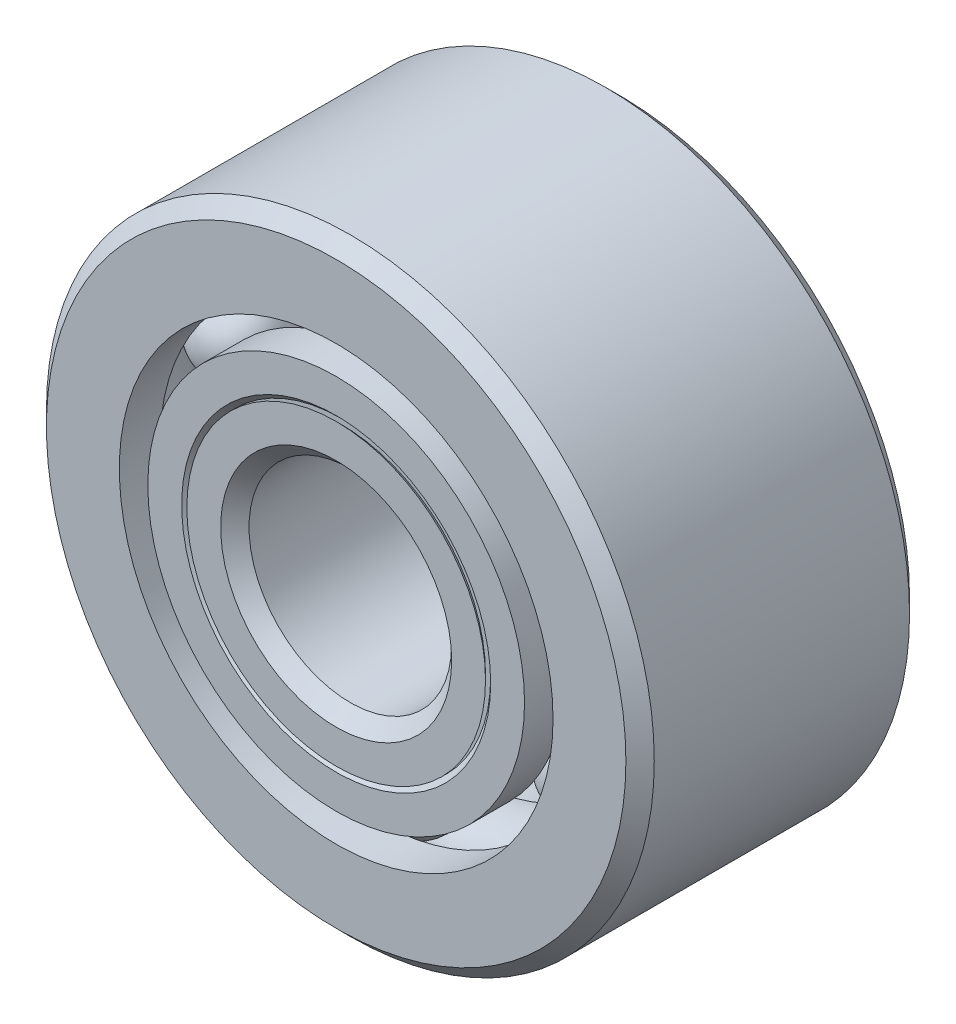
SolidWorks part; units mm, degrees
note: '?' marks a value the reader was unsure of.
ref_plane "Front Plane" through (0, 0, 0) normal (0, 0, 1) x (1, 0, 0)
ref_plane "Top Plane" through (0, 0, 0) normal (0, 1, 0) x (1, 0, 0)
ref_plane "Right Plane" through (0, 0, 0) normal (1, 0, 0) x (0, 0, -1)
sketch "Sketch1" plane through (0, 0, 0) normal (1, 0, 0) x (0, 0, -1)
  line L0 (-7, 0) -> (7, 0) construction
  line L1 (0, 15) -> (0, -15) construction
  line L2 (6.3, 15) -> (-6.3, 15)
  line L3 (-6.3, 15) -> (-7, 14.3)
  line L4 (-7, 14.3) -> (-7, 10.7033)
  line L5 (-7, 10.7033) -> (-5, 10.7033)
  line L6 (7, 10.7033) -> (5, 10.7033)
  line L7 (7, 14.3) -> (7, 10.7033)
  line L8 (6.3, 15) -> (7, 14.3)
  line L9 (0, 15) -> (0, 10) construction
  line L10 (0, 10) -> (0, 5) construction
  line L11 (-1, 10.7033) -> (1, 10.7033)
  line L12 (-3, 10) -> (-3, 9.2967) construction
  line L13 (-3, 10) -> (-3, 10.7033) construction
  arc A1 (-5, 10.7033) -> (-1, 10.7033) centre (-3, 10) cw
  arc A2 (1, 10.7033) -> (5, 10.7033) centre (3, 10) cw
  point P14 (0, 5)
  dimension "locating bearing hieght" = 14
  dimension "locating bearing od" = 30
  dimension "D1" = 45
  dimension "D2" = 0.7
  dimension "D3" = 4
  dimension "D4" = 0.7033
revolve "Revolve1" add sketch "Sketch1" angle 360 about L0
sketch "Sketch3" plane through (0, 0, 0) normal (1, 0, 0) x (0, 0, -1)
  line L0 (-1, 9.2967) -> (1, 9.2967)
  line L2 (-7, 9.2967) -> (-5, 9.2967)
  line L5 (-7, 9.2967) -> (-7, 7.6254)
  line L6 (-6.3, 5) -> (6.3, 5)
  line L8 (7, 9.2967) -> (7, 5.7)
  line L10 (5, 9.2967) -> (7, 9.2967)
  line L11 (-7, 7.3714) -> (-6.746, 7.1174)
  line L12 (-6.746, 7.1174) -> (-6.746, 7.3714)
  line L13 (-6.746, 7.3714) -> (-7, 7.6254)
  line L16 (-7, 7.3714) -> (-7, 5.7)
  line L17 (7, 5.7) -> (6.3, 5)
  line L18 (-6.3, 5) -> (-7, 5.7)
  line L19 (6.3, 15) -> (7, 14.3) construction
  line L20 (-6.3, 15) -> (-7, 14.3) construction
  line L21 (7, -14.3) -> (7, 14.3) construction
  arc A0 (-5, 9.2967) -> (-1, 9.2967) centre (-3, 10) ccw
  arc A2 (1, 9.2967) -> (5, 9.2967) centre (3, 10) ccw
  arc A4 (-1, 10.7033) -> (-5, 10.7033) centre (-3, 10) ccw construction
  arc A5 (5, 10.7033) -> (1, 10.7033) centre (3, 10) ccw construction
  dimension "D1" = 0.254
  dimension "D2" = 0.254
revolve "Revolve3" add sketch "Sketch3" angle 360 about L0
sketch "Sketch4" plane through (0, 0, 0) normal (1, 0, 0) x (0, 0, -1)
  line L0 (-0.8799, 10) -> (0.8799, 10) construction
  line L1 (-5.1201, 10) -> (-0.8799, 10)
  line L2 (0.8799, 10) -> (5.1201, 10)
  arc A0 (5.1201, 10) -> (0.8799, 10) centre (3, 10) ccw
  arc A4 (-0.8799, 10) -> (-5.1201, 10) centre (-3, 10) ccw
  arc A5 (-1, 10.7033) -> (-5, 10.7033) centre (-3, 10) ccw construction
  arc A6 (5, 10.7033) -> (1, 10.7033) centre (3, 10) ccw construction
revolve "Revolve4" add sketch "Sketch4" angle 360 about L0
ref_axis "Axis1" through (0, 0, -7) along (0, 0, 1)?
pattern_circular "CirPattern1" count 6 every 60 about axis through (0, 0, 0) along (0, 0, 1)
equation "\"D2@Sketch1\" = \"locating bearing hieght@Sketch1\" * .05"
equation "\"D3@Sketch1\" = \"locating bearing hieght@Sketch1\" / 3.5"
equation "\"D4@Sketch1\" =  (  (  ( \"locating bearing od@Sketch1\" - \"locating bearing hieght@Sketch1\" )  / 2 )  / 3.25 )  / 3.5"
equation "\"D2@CirPattern1\" = 360/\"Balls@CirPattern1\""
equation "\"locating bearing hieght\"= \"locating bearing hieght@Sketch1\""
